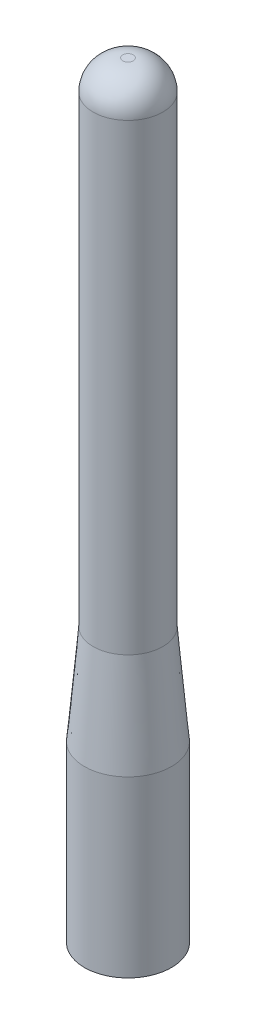
SolidWorks part; units mm, degrees
ref_plane "Front Plane" through (0, 0, 0) normal (0, 0, 1) x (1, 0, 0)
ref_plane "Top Plane" through (0, 0, 0) normal (0, 1, 0) x (1, 0, 0)
ref_plane "Right Plane" through (0, 0, 0) normal (1, 0, 0) x (0, 0, -1)
sketch "Sketch1" plane through (0, 0, 0) normal (0, 1, 0) x (1, 0, 0)
  circle A0 centre (0, 0) radius 5
extrude "Boss-Extrude1" add sketch "Sketch1" along normal blind 20
sketch "Sketch2" plane through (0, 20, 0) normal (0, 1, 0) x (1, 0, 0)
  circle A0 centre (0, 0) radius 4
extrude "Boss-Extrude2" add sketch "Sketch2" along normal blind 68
fillet "Fillet1" radius 3.4 1 edges at (0, 88, 4)
chamfer "Chamfer1" distance 1 angle 85 1 edges at (0, 20, 4) first distance on face at (0, 20, 4)
sketch "Sketch3" plane through (0, 0, 0) normal (0, -1, 0) x (-1, 0, 0)
  line L1 (-2.5, -2.5) -> (2.5, -2.5)
  line L2 (-2.5, -2.5) -> (-2.5, 2.5)
  line L3 (-2.5, 2.5) -> (2.5, 2.5)
  line L4 (2.5, -2.5) -> (2.5, 2.5)
  line L5 (-2.5, -2.5) -> (2.5, 2.5) construction
  line L6 (-2.5, 2.5) -> (2.5, -2.5) construction
  point P0 (0, 0)
  dimension "D1" = 5
  dimension "D2" = 5
  dimension "D3" = 5
extrude "Cut-Extrude1" cut sketch "Sketch3" against normal blind 8
sketch "Sketch4" plane through (0, 0, 0) normal (0, -1, 0) x (-1, 0, 0)
  line L1 (2.5, 2.5) -> (-2.5, 2.5)
  line L2 (2.5, 2.5) -> (2.5, 5.2024)
  line L3 (2.5, 5.2024) -> (-2.5, 5.2024)
  line L4 (-2.5, 2.5) -> (-2.5, 5.2024)
  dimension "D1" = 5
extrude "Cut-Extrude2" cut sketch "Sketch4" against normal blind 8
sketch "Sketch5" plane through (2.5, 0, 0) normal (-1, 0, 0) x (0, 0, 1)
  circle A0 centre (0, 5.5) radius 0.5
extrude "Boss-Extrude3" add sketch "Sketch5" along normal blind 5
